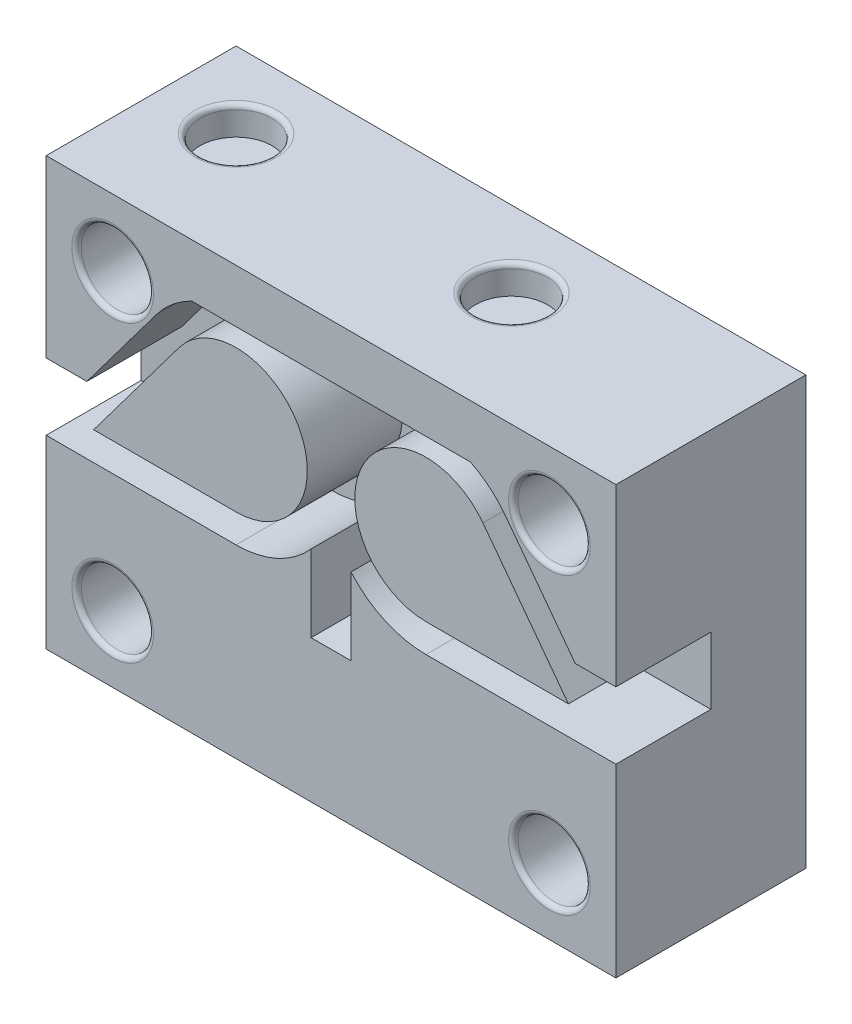
SolidWorks part; units mm, degrees
ref_plane "Front Plane" through (0, 0, 0) normal (0, 0, 1) x (1, 0, 0)
ref_plane "Top Plane" through (0, 0, 0) normal (0, 1, 0) x (1, 0, 0)
ref_plane "Right Plane" through (0, 0, 0) normal (1, 0, 0) x (0, 0, -1)
sketch "Sketch1" plane through (0, 0, 0) normal (0, 0, 1) x (1, 0, 0)
  line L0 (-37.3657, 7.5) -> (34.9105, 7.5) construction
  line L1 (-30, -22.5) -> (30, -22.5)
  line L2 (-30, -22.5) -> (-30, 22.5)
  line L3 (-30, 22.5) -> (30, 22.5)
  line L4 (30, -22.5) -> (30, 22.5)
  line L5 (-30, -22.5) -> (30, 22.5) construction
  line L6 (-30, 22.5) -> (30, -22.5) construction
  line L7 (-10, 29.4537) -> (-10, -35.1207) construction
  line L8 (0, 22.5) -> (0, -27.0967) construction
  line L9 (-10, 0) -> (-25, 0)
  line L10 (-25, 0) -> (-16, 12)
  line L11 (25, 0) -> (16, 12)
  line L12 (10, 0) -> (25, 0)
  line L13 (-30, -3) -> (-10, -3)
  line L15 (2.1006, 0.5827) -> (2.1003, -7.5128)
  line L16 (30, -16.875) -> (30, -3)
  line L17 (10, -3) -> (30, -3)
  line L18 (-10, -3) -> (-30, -3)
  line L19 (-2.1006, 0.5827) -> (-2.1006, -7.5128)
  line L20 (-2.1006, -7.5128) -> (2.1003, -7.5128)
  line L21 (-30, 4.0476) -> (-25.7143, 4.0476)
  line L30 (-25.7143, 4.0476) -> (-18.4, 13.8)
  line L31 (-14.6784, 22.5) -> (-14.6784, 16.9001)
  line L32 (30, 4.0476) -> (25.7143, 4.0476)
  line L33 (25.7143, 4.0476) -> (18.4, 13.8)
  line L34 (14.6784, 22.5) -> (14.6784, 16.9001)
  line L35 (-14.6784, 16.9001) -> (14.6784, 16.9001)
  line L36 (-30, 0) -> (30, 0) construction
  circle A0 centre (-10, 7.5) radius 7.5
  circle A1 centre (10, 7.5) radius 7.5
  arc A2 (2.1006, 0.5827) -> (10, -3) centre (10, 7.5) ccw
  arc A3 (-2.1006, 0.5827) -> (-10, -3) centre (-10, 7.5) cw
  arc A4 (-18.4, 13.8) -> (-14.6784, 16.9001) centre (-10, 7.5) cw
  arc A5 (18.4, 13.8) -> (14.6784, 16.9001) centre (10, 7.5) ccw
  circle A6 centre (-23, 15.5) radius 3.8
  circle A7 centre (23, 15.5) radius 3.8
  circle A8 centre (23, -15.5) radius 3.8
  circle A9 centre (-23, -15.5) radius 3.8
  point P0 (0, 0)
  dimension "D5" = 15
  dimension "D8" = 10.5
  dimension "D7" = 7.6
  dimension "D2" = 45
  dimension "D3" = 15
  dimension "D4" = 20
  dimension "D6" = 15
  dimension "D12" = 4.2009
  dimension "D20" = 3
  dimension "D21" = 10.5
  dimension "D23" = 4.2857
  dimension "D24" = 15.3216
  dimension "D9" = 7
  dimension "D10" = 7
  dimension "D11" = 60
  dimension "D13" = 8.0954
extrude "Boss-Extrude1" add sketch "Sketch1" along normal blind 20 contours A5 L33 L32 L4 L3 L34 A7 | L30 A4 L31 L3 L2 L21 A6 | L19 A3 L13 L2 L1 L4 L17 A2 L15 L20 A8 A9 | L31 L35 L34 L3 | A0 | A0 L10 L9 | A1 | L11 A1 L12 region at (0, -12.4766, 0) region at (-29.7602, 13.2738, 0) region at (27.8571, 4.2875, 0) region at (0, 19.7001, 0) region at (-18.9601, 3.02, 0) region at (-10, 7.5, 0) region at (18.9601, 3.02, 0) region at (10, 7.5, 0)
extrude "Boss-Extrude2" add sketch "Sketch1<6>" along normal blind 10 contours L33 A5 L35 A4 L30 L21 L2 L13 A3 L19 L20 L15 A2 L17 L4 L32 A0 L9 L10 L12 A1 L11 region at (0, 4.9915, 0)
sketch "Sketch1<6>" plane through (0, 0, 0) normal (0, 0, 1) x (1, 0, 0) same geometry as "Sketch1"
fillet "Fillet1" radius 0.5 8 edges at (-19.2, -15.5, 0) (26.8, -15.5, 0) (26.8, 15.5, 0) (-19.2, 15.5, 0) (26.8, -15.5, 20) (26.8, 15.5, 20) (-19.2, -15.5, 20) (-19.2, 15.5, 20)
sketch "Sketch2" plane through (0, 22.5, 0) normal (0, 1, 0) x (1, 0, 0)
  line L0 (-30, -20) -> (-30, 0) construction
  line L1 (-30, 0) -> (30, 0) construction
  circle A0 centre (-22, -8) radius 3.8
  circle A1 centre (7, -8) radius 3.8
  dimension "D5" = 7.6
  dimension "D6" = 7.6
  dimension "D1" = 8
  dimension "D2" = 8
  dimension "D3" = 8
  dimension "D4" = 29
extrude "Cut-Extrude1" cut sketch "Sketch2" against normal blind 3
fillet "Fillet2" radius 0.5 2 edges at (7, 22.5, 11.8) (-22, 22.5, 11.8)
equation "\"hftd\"= 5"
equation "\"hftdb\"= 8"
equation "\"hfth\"= 8"
equation "\"hftdb2\"= 29"
equation "\"D2@Sketch1\"=\"H\""
equation "\"D3@Sketch1\"=\"dh\""
equation "\"D5@Sketch1\"=\"r\""
equation "\"D8@Sketch1\"=\"r2\""
equation "\"D20@Sketch1\"=\"b\""
equation "\"D21@Sketch1\"=\"r2\""
equation "\"W\" = 60"
equation "\"H\" = 45"
equation "\"dh\"= 1 / 3 * \"H\""
equation "\"dw\"= 1 / 3 * \"W\""
equation "\"r\"= 15"
equation "\"b\"= 3"
equation "\"r2\"= \"r\" / 2 + \"b\""
equation "\"bhg\"= 1 / 8 * \"H\""
equation "\"bwg\"= \"W\" / 2 - 2.1"
equation "\"D11@Sketch1\"=\"W\""
